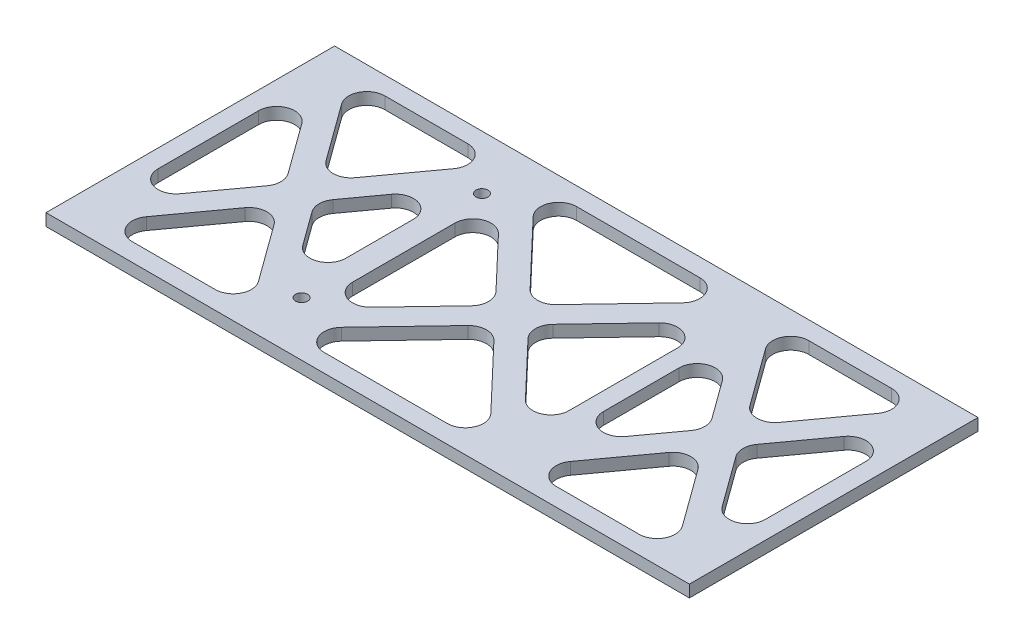
SolidWorks part; units mm, degrees
material "Beech"
ref_plane "Front Plane" through (0, 0, 0) normal (0, 0, 1) x (1, 0, 0)
ref_plane "Top Plane" through (0, 0, 0) normal (0, 1, 0) x (1, 0, 0)
ref_plane "Right Plane" through (0, 0, 0) normal (1, 0, 0) x (0, 0, -1)
sketch "Sketch1" plane through (0, 0, 0) normal (0, 1, 0) x (1, 0, 0)
  line L0 (-50.8, 60.96) -> (-50.8, -60.96) construction
  line L1 (135.89, 60.96) -> (-135.89, 60.96)
  line L2 (135.89, 60.96) -> (135.89, -60.96)
  line L3 (135.89, -60.96) -> (-135.89, -60.96)
  line L4 (-135.89, 60.96) -> (-135.89, -60.96)
  line L5 (135.89, 60.96) -> (-135.89, -60.96) construction
  line L6 (135.89, -60.96) -> (-135.89, 60.96) construction
  line L7 (0, 0) -> (-135.89, 0) construction
  line L8 (128.27, 53.34) -> (-128.27, 53.34)
  line L9 (-128.27, 53.34) -> (-128.27, -53.34)
  line L10 (128.27, -53.34) -> (-128.27, -53.34)
  line L11 (128.27, 53.34) -> (128.27, -53.34)
  line L12 (50.8, 60.96) -> (50.8, -60.96) construction
  line L13 (-128.27, 53.34) -> (-50.8, -53.34) construction
  line L14 (-128.27, -53.34) -> (-50.8, 53.34) construction
  line L15 (-50.8, 53.34) -> (50.8, -53.34) construction
  line L16 (-50.8, -53.34) -> (50.8, 53.34) construction
  line L17 (50.8, 53.34) -> (128.27, -53.34) construction
  line L18 (50.8, -53.34) -> (128.27, 53.34) construction
  line L19 (-132.3805, 50.355) -> (-51.3271, -61.2595)
  line L20 (-51.3271, -61.2595) -> (50.2729, 45.4205)
  line L21 (50.2729, 45.4205) -> (124.1595, -56.325)
  line L22 (-124.1595, -56.325) -> (-50.2729, 45.4205)
  line L23 (-50.2729, 45.4205) -> (51.3271, -61.2595)
  line L24 (51.3271, -61.2595) -> (132.3805, 50.355)
  line L25 (-55.88, 60.96) -> (-55.88, -60.96)
  line L26 (46.99, 60.96) -> (46.99, -60.96)
  line L27 (-124.1595, 56.325) -> (-50.2729, -45.4205)
  line L28 (-50.2729, -45.4205) -> (51.3271, 61.2595)
  line L29 (51.3271, 61.2595) -> (132.3805, -50.355)
  line L30 (-132.3805, -50.355) -> (-51.3271, 61.2595)
  line L31 (-51.3271, 61.2595) -> (50.2729, -45.4205)
  line L32 (50.2729, -45.4205) -> (124.1595, 56.325)
  line L33 (-45.72, 60.96) -> (-45.72, -60.96)
  line L34 (54.61, 60.96) -> (54.61, -60.96)
  circle A0 centre (-50.8, 38.1) radius 2.54
  circle A1 centre (-50.8, -38.1) radius 2.54
  point P0 (0, 0)
  dimension "D5" = 5.08
  dimension "D6" = 5.08
  dimension "D1" = 121.92
  dimension "D2" = 271.78
  dimension "D3" = 38.1
  dimension "D4" = 38.1
  dimension "D8" = 50.8
  dimension "tbd gear dim" = 50.8
  dimension "D11" = 5.08
  dimension "D12" = 5.08
  dimension "D7" = 7.62
  dimension "D9" = 3.81
  dimension "D10" = 3.81
  dimension "D13" = 5.08
  dimension "D14" = 5.08
extrude "Boss-Extrude1" add sketch "Sketch1" along normal blind 5.08 contours L33 L23 L22 L25 L27 L28 A1 A0 | L30 L27 L22 L25 L8 | L30 L19 L22 L27 | L30 L9 L10 L22 L19 | L19 L30 L27 L8 L9 | L27 L22 L19 L10 L25 | L33 L28 L27 L25 L10 | L25 L10 L19 | L33 L10 L25 L19 L3 L20 | L10 L33 L20 | L28 L33 L10 L20 L23 | L20 L33 L3 L26 L23 L10 | L33 L20 L3 | L19 L25 L3 | L8 L30 L25 L1 L4 L3 L19 L10 L9 | L30 L8 L25 | L33 L31 L1 L30 L25 L8 | L31 L33 L8 | L33 L1 L31 | L25 L30 L1 | L33 L8 L25 L22 L23 | L8 L33 L23 L28 L31 | L1 L33 L31 L8 L28 L26 | L31 L28 L23 L20 | L28 L31 L20 L26 L8 | L31 L20 L23 L10 L26 | L26 L10 L23 | L10 L34 L24 | L34 L10 L26 L23 L3 L24 | L34 L24 L3 | L23 L26 L3 | L34 L32 L31 L26 L10 | L32 L34 L10 L24 L21 | L1 L34 L29 L8 L11 L10 L24 L3 L2 | L34 L21 L20 L26 L31 L32 | L28 L8 L26 | L34 L29 L1 L28 L26 L8 | L26 L28 L1 | L34 L1 L29 | L29 L34 L8 | L34 L8 L26 L20 L21 | L8 L34 L21 L32 L29 | L32 L29 L24 L11 L8 | L32 L21 L24 L29 | L29 L24 L21 L10 L11 region at (134.4247, 0, 0) region at (53.5882, 0, -59.5529) region at (50.8735, 0, -56.3085) region at (55.4327, 0, -54.4729) region at (53.5882, 0, 59.5529) region at (48.3406, 0, -59.5418) region at (70.6709, 0, -26.2058) region at (50.9932, 0, -48.0381) region at (50.8735, 0, 56.3085) region at (55.4327, 0, 54.4729) region at (0.4142, 0, -57.1796) region at (45.9216, 0, -54.4618) region at (109.6993, 0, -27.7673) region at (89.535, 0, 0) region at (25.0257, 0, -26.4237) region at (50.7534, 0, 0) region at (48.3406, 0, 59.5418) region at (70.6709, 0, 26.2058) region at (50.9932, 0, 48.0381) region at (-47.494, 0, -59.0973) region at (109.6993, 0, 27.7673) region at (0.4142, 0, 57.1796) region at (45.9216, 0, 54.4618) region at (25.0257, 0, 26.4237) region at (-50.8427, 0, -56.0915) region at (-45.0749, 0, -54.0173) region at (-24.5002, 0, -25.9086) region at (0, 0, 0) region at (-47.494, 0, 59.0973) region at (-54.4349, 0, -58.97) region at (-51.0721, 0, -47.5937) region at (-24.5002, 0, 25.9086) region at (-50.8427, 0, 56.0915) region at (-45.0749, 0, 54.0173) region at (-57.3383, 0, -57.975) region at (-56.2794, 0, -53.89) region at (-71.2198, 0, -25.5028) region at (-50.7248, 0, 0) region at (-51.0721, 0, 47.5937) region at (-54.4349, 0, 58.97) region at (-56.2794, 0, 53.89) region at (-71.2198, 0, 25.5028) region at (-109.6993, 0, -27.7673) region at (-89.535, 0, 0) region at (-109.6993, 0, 27.7673)
fillet "Fillet1" radius 7.62 36 edges at (54.61, 2.54, 39.4481) (89.535, 2.54, -8.6454) (0, 2.54, -7.366) (-55.88, 2.54, -37.6992) (-121.9918, 2.54, -53.34) (-43.7848, 2.54, -53.34) (-45.72, 2.54, 40.64) (-55.88, 2.54, 37.6992) (-89.535, 2.54, -8.6454) (-89.535, 2.54, 8.6454) (0, 2.54, 7.366) (89.535, 2.54, 8.6454) (128.27, 2.54, -44.6946) (57.0782, 2.54, -53.34) (54.61, 2.54, -39.4481) (46.99, 2.54, -41.9735) (-45.72, 2.54, -40.64) (46.99, 2.54, 41.9735) (-83.2568, 2.54, 0) (95.8132, 2.54, 0) (7.0152, 2.54, 0) (-43.7848, 2.54, 53.34) (-121.9918, 2.54, 53.34) (57.0782, 2.54, 53.34) (128.27, 2.54, 44.6946) (121.9918, 2.54, 53.34) (-57.0782, 2.54, 53.34) (43.7848, 2.54, 53.34) (-7.0152, 2.54, 0) (83.2568, 2.54, 0) (121.9918, 2.54, -53.34) (43.7848, 2.54, -53.34) (-57.0782, 2.54, -53.34) (-95.8132, 2.54, 0) (-128.27, 2.54, 44.6946) (-128.27, 2.54, -44.6946)
